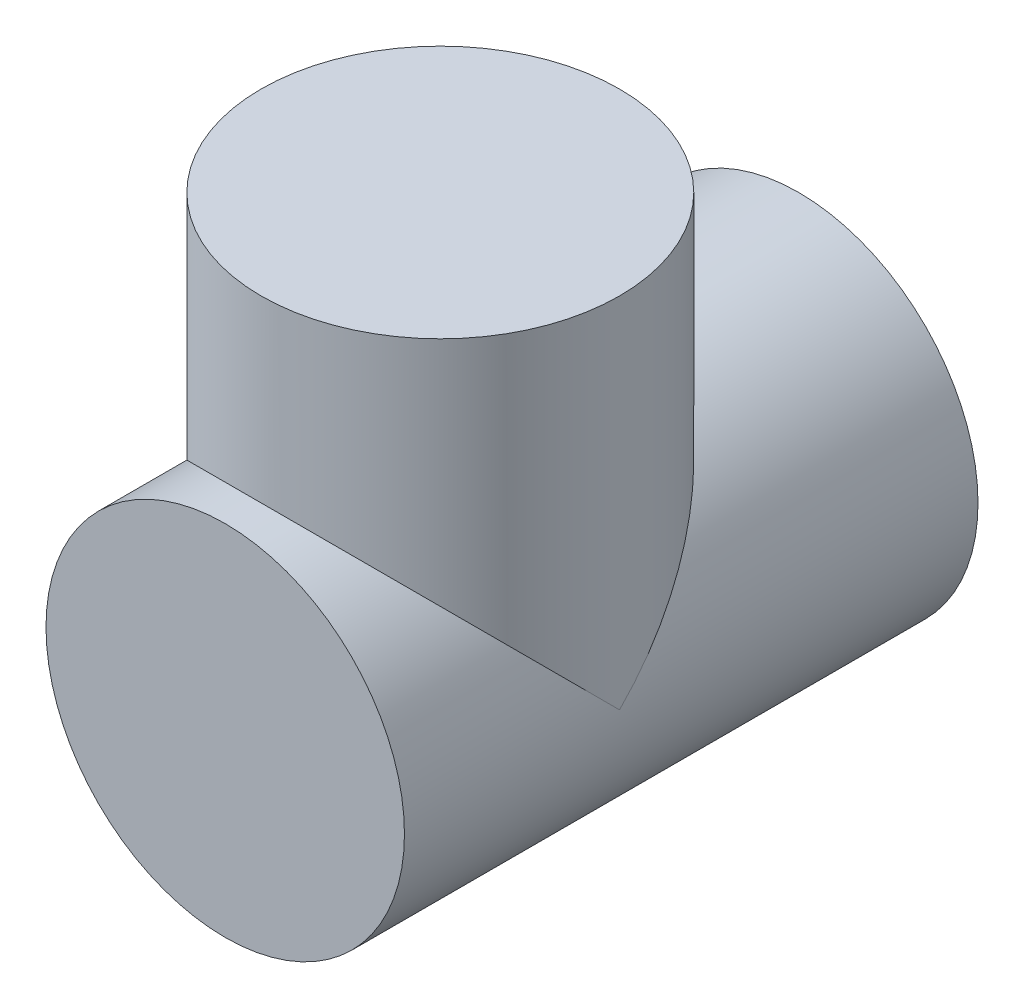
SolidWorks part; units mm, degrees
ref_plane "前视基准面" through (0, 0, 0) normal (0, 0, 1) x (1, 0, 0)
ref_plane "上视基准面" through (0, 0, 0) normal (0, 1, 0) x (1, 0, 0)
ref_plane "右视基准面" through (0, 0, 0) normal (1, 0, 0) x (0, 0, -1)
sketch "草图1" plane through (0, 0, 0) normal (0, 0, 1) x (1, 0, 0)
  circle A0 centre (0, 0) radius 250
extrude "凸台-拉伸1" add sketch "草图1" along normal blind 800
sketch "草图2" plane through (0, 0, 0) normal (0, 1, 0) x (1, 0, 0)
  circle A0 centre (0, -500) radius 250
  dimension "D1" = 500
  dimension "D2" = 0
extrude "凸台-拉伸2" add sketch "草图2" along normal blind 500
ref_axis "基准轴1" through (0, 0, 800) along (0, 0, -1)
ref_axis "基准轴2" through (0, 500, 500) along (0, -1, 0)
ref_point "点1"
